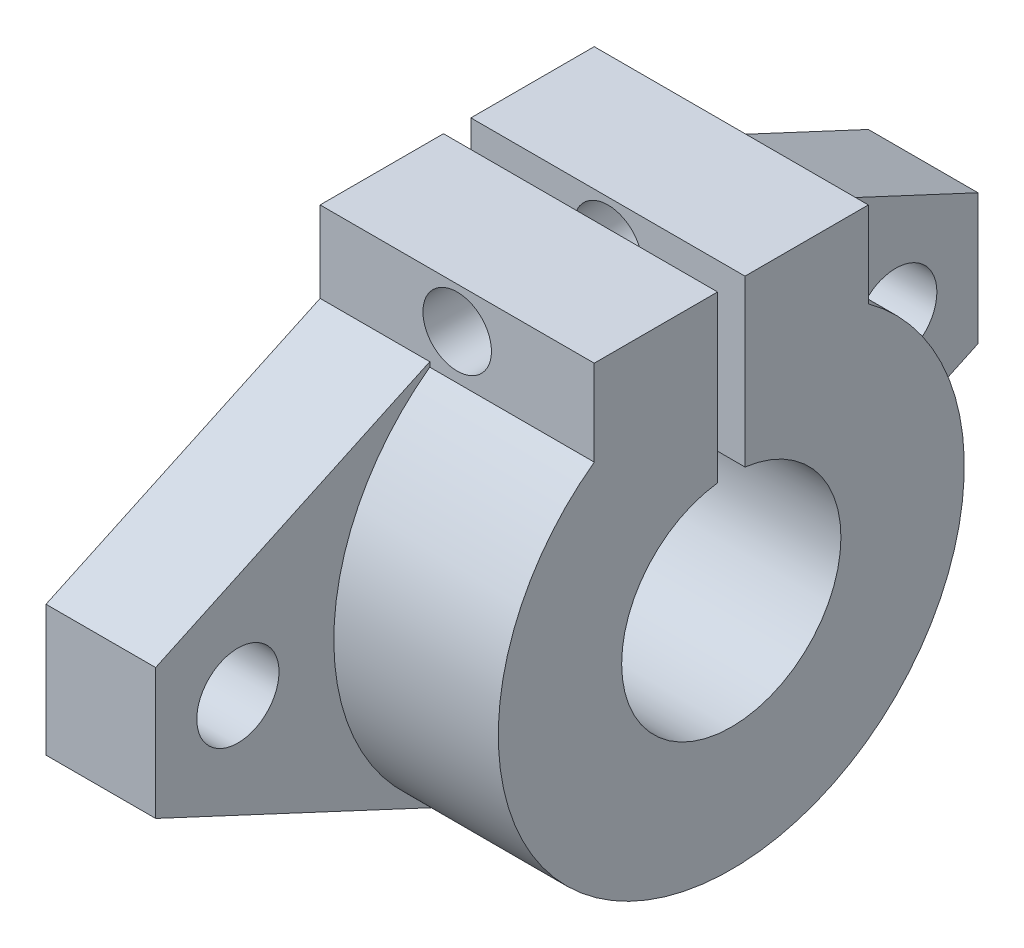
SolidWorks part; units mm, degrees
material "6061 合金"
ref_plane "前视基准面" through (0, 0, 0) normal (0, 0, 1) x (1, 0, 0)
ref_plane "上视基准面" through (0, 0, 0) normal (0, 1, 0) x (1, 0, 0)
ref_plane "右视基准面" through (0, 0, 0) normal (1, 0, 0) x (0, 0, -1)
sketch "草图1" plane through (0, 0, 0) normal (1, 0, 0) x (0, 0, -1)
  line L0 (-51.8991, 0) -> (49.8448, 0) construction
  line L1 (0, 31.9917) -> (0, -30.8598) construction
  line L2 (-30, 4.7682) -> (-30, -4.7682)
  line L3 (-7.1845, 15.4072) -> (-30, 4.7682)
  line L4 (-7.1845, -15.4072) -> (-30, -4.7682)
  line L5 (7.1845, -15.4072) -> (30, -4.7682)
  line L6 (30, 4.7682) -> (30, -4.7682)
  line L7 (7.1845, 15.4072) -> (30, 4.7682)
  circle A0 centre (0, 0) radius 17
  circle A1 centre (0, 0) radius 8
  circle A2 centre (-24, 0) radius 3
  circle A3 centre (24, 0) radius 3
  dimension "D1" = 16
  dimension "D2" = 34
  dimension "D3" = 48
  dimension "D4" = 6
  dimension "D5" = 60
  dimension "D6" = 115
extrude "凸台-拉伸1" add sketch "草图1" along normal blind 8 contours A0 L3 L2 L4 A2 | A0 L5 L6 L7 A3 region at (0, 9.7402, 18.4302) region at (0, 9.7402, -18.4302)
extrude "凸台-拉伸2" add sketch "草图1<3>" along normal blind 20 contours A0 A1 region at (0, 16.5192, 0)
sketch "草图1<3>" plane through (0, 0, 0) normal (1, 0, 0) x (0, 0, -1) same geometry as "草图1"
ref_plane "基准面1" through (0, 20, 0) normal (0, 1, 0) x (1, 0, 0)
sketch "草图2" plane through (0, 20, 0) normal (0, 1, 0) x (1, 0, 0)
  line L0 (0, 0) -> (20, 0) construction
  line L1 (20, -17) -> (20, 17) construction
  line L3 (0, -10) -> (20, -10)
  line L4 (0, -10) -> (0, 10)
  line L5 (0, 10) -> (20, 10)
  line L6 (20, -10) -> (20, 10)
  line L7 (0, -10) -> (20, 10) construction
  line L8 (0, 10) -> (20, -10) construction
  point P5 (10, 0)
  dimension "D1" = 20
extrude "凸台-拉伸3" add sketch "草图2" against normal up to next contours L5 L6 L3 L4
sketch "草图3" plane through (0, 20, 0) normal (0, 1, 0) x (1, 0, 0)
  line L0 (0, 0) -> (20, 0) construction
  line L1 (20, -10) -> (20, 10) construction
  line L3 (0, -1) -> (20, -1)
  line L4 (0, -1) -> (0, 1)
  line L5 (0, 1) -> (20, 1)
  line L6 (20, -1) -> (20, 1)
  line L7 (0, -1) -> (20, 1) construction
  line L8 (0, 1) -> (20, -1) construction
  point P5 (10, 0)
  dimension "D1" = 2
extrude "切除-拉伸1" cut sketch "草图3" against normal blind 20
sketch "草图4" plane through (0, 0, 10) normal (0, 0, 1) x (1, 0, 0)
  line L0 (0, 18.6834) -> (20, 18.6834) construction
  line L1 (0, 14.0943) -> (0, 20) construction
  line L2 (20, 13.7477) -> (20, 20) construction
  line L3 (10, 18.6834) -> (10, 15.3166) construction
  line L4 (11, 20) -> (-11, 20) construction
  circle A0 centre (10, 17) radius 2.5
  dimension "D1" = 5
  dimension "D2" = 3
extrude "切除-拉伸2" cut sketch "草图4" against normal through all contours A0
